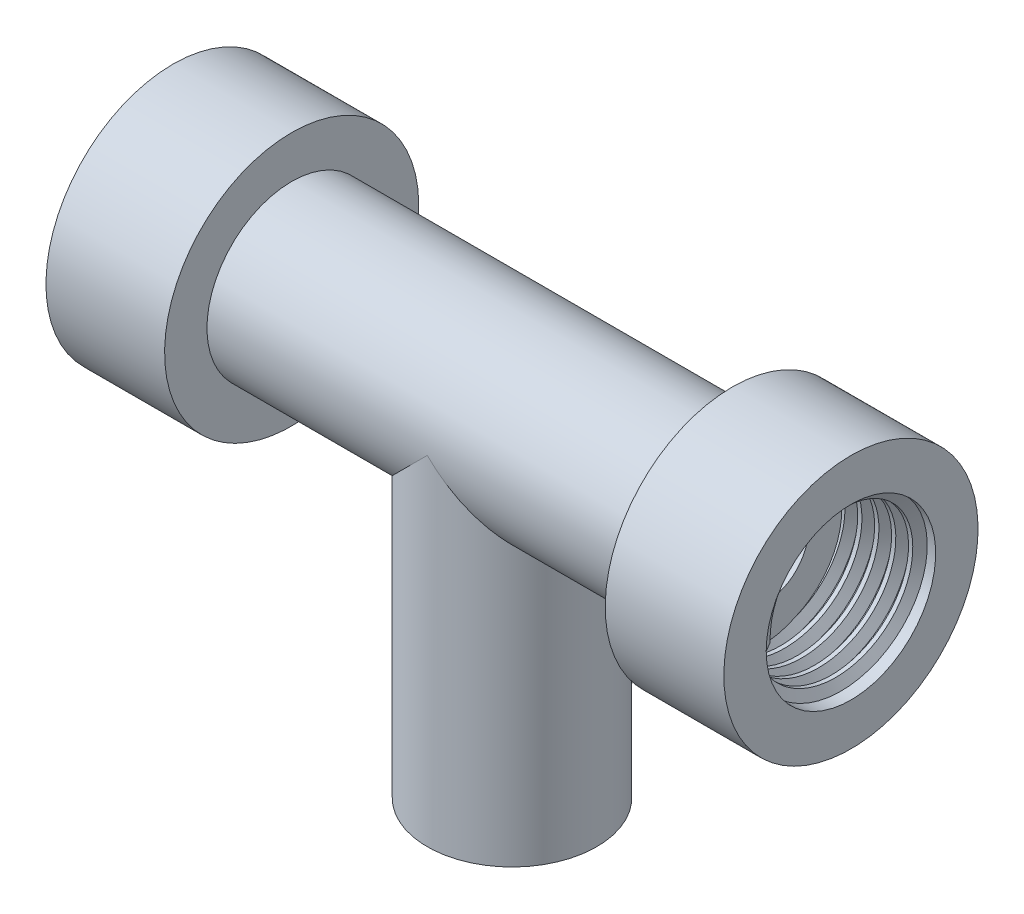
SolidWorks part; units mm, degrees
ref_plane "Front Plane" through (0, 0, 0) normal (0, 0, 1) x (1, 0, 0)
ref_plane "Top Plane" through (0, 0, 0) normal (0, 1, 0) x (1, 0, 0)
ref_plane "Right Plane" through (0, 0, 0) normal (1, 0, 0) x (0, 0, -1)
sketch "Sketch2" plane through (0, 0, 0) normal (0, 0, 1) x (1, 0, 0)
  line L1 (-3.175, -12.7) -> (3.175, -12.7)
  line L2 (-3.175, -12.7) -> (-3.175, 12.7)
  line L3 (-3.175, 12.7) -> (3.175, 12.7)
  line L4 (3.175, -12.7) -> (3.175, 12.7)
  line L5 (-3.175, -12.7) -> (3.175, 12.7) construction
  line L6 (-3.175, 12.7) -> (3.175, -12.7) construction
  point P0 (0, 0)
  dimension "D1" = 6.35
  dimension "D2" = 25.4
revolve "Revolve1" add sketch "Sketch2" angle 360 about L4
sketch "Sketch4" plane through (0, 0, 0) normal (0, 0, 1) x (1, 0, 0)
  line L0 (3.175, 12.7) -> (3.175, 6.35)
  line L1 (9.525, 12.7) -> (-3.175, 12.7) construction
  line L2 (3.175, 6.35) -> (19.685, 6.35)
  line L3 (19.685, 6.35) -> (19.685, 3.175)
  line L4 (19.685, 3.175) -> (28.575, 3.175)
  line L5 (28.575, 3.175) -> (28.575, 6.35)
  line L6 (28.575, 6.35) -> (22.225, 6.35)
  line L7 (22.225, 6.35) -> (22.225, 12.7)
  line L8 (22.225, 12.7) -> (3.175, 12.7)
  dimension "D1" = 6.35
  dimension "D2" = 3.175
  dimension "D3" = 6.35
  dimension "D4" = 6.35
  dimension "D5" = 19.05
  dimension "D6" = 16.51
revolve "Revolve2" add sketch "Sketch4" angle 360 about L8
mirror "Mirror1" about plane through (3.175, 12.7, 0) normal (1, 0, 0) of "Revolve2"
sketch "Sketch6" plane through (0, -12.7, 0) normal (0, -1, 0) x (1, 0, 0)
  circle A1 centre (3.175, 0) radius 3.175
  circle A2 centre (3.175, 0) radius 6.35 construction
  point P2 (3.5853, -0.7575)
  point P3 (3.4812, 0.2894)
  dimension "D2" = 6.35
  dimension "D1" = 0
extrude "Cut-Extrude1" cut sketch "Sketch6" against normal blind 25.4
sketch "Sketch7" plane through (22.225, 0, 0) normal (1, 0, 0) x (0, 0, -1)
  circle A0 centre (0, 12.7) radius 3.175
  circle A2 centre (0, 12.7) radius 6.35 construction
  dimension "D1" = 6.35
  dimension "D2" = 0
extrude "Cut-Extrude2" cut sketch "Sketch7" against normal blind 44.704
thread "Thread1" pitch 1.27 method extrude profile "Thread Profile2" start angle 0, offset 0, length 0, pitch 1.27, diameter 12.7
ref_plane "Plane3" through (28.575, 12.7, 6.35) normal (0, -1, 0) x (0, 0, 1)
sketch "Thread Profile2" plane through (28.575, 12.7, 6.35) normal (0, -1, 0) x (0, 0, 1)
  line L0 (0, 0) -> (0, 1.27) construction
  line L11 (0, 0) -> (0, 1.1112)
  line L12 (0, 1.1112) -> (-0.6874, 0.7144)
  line L13 (-0.6874, 0.7144) -> (-0.6874, 0.3969)
  line L15 (-0.6874, 0.3969) -> (0, 0)
  line L17 (-0.6874, 0.5556) -> (0, 0.5556) construction
  point P2 (0, 0)
  dimension "Pitch" = 1.27
  dimension "Profile_Angle" = 60
  dimension "Profile_Land" = 0.3175
  dimension "Profile_Height" = 0.6874
thread "Thread2" pitch 1.27 method extrude profile "Thread Profile3" start angle 0, offset 0, length 0, pitch 1.27, diameter 12.7
ref_plane "Plane4" through (-22.225, 12.7, -6.35) normal (0, -1, 0) x (0, 0, -1)
sketch "Thread Profile3" plane through (-22.225, 12.7, -6.35) normal (0, -1, 0) x (0, 0, -1)
  line L0 (0, 0) -> (0, 1.27) construction
  line L11 (0, 0) -> (0, 1.1112)
  line L12 (0, 1.1112) -> (-0.6874, 0.7144)
  line L13 (-0.6874, 0.7144) -> (-0.6874, 0.3969)
  line L15 (-0.6874, 0.3969) -> (0, 0)
  line L17 (-0.6874, 0.5556) -> (0, 0.5556) construction
  point P2 (0, 0)
  dimension "Pitch" = 1.27
  dimension "Profile_Angle" = 60
  dimension "Profile_Land" = 0.3175
  dimension "Profile_Height" = 0.6874
